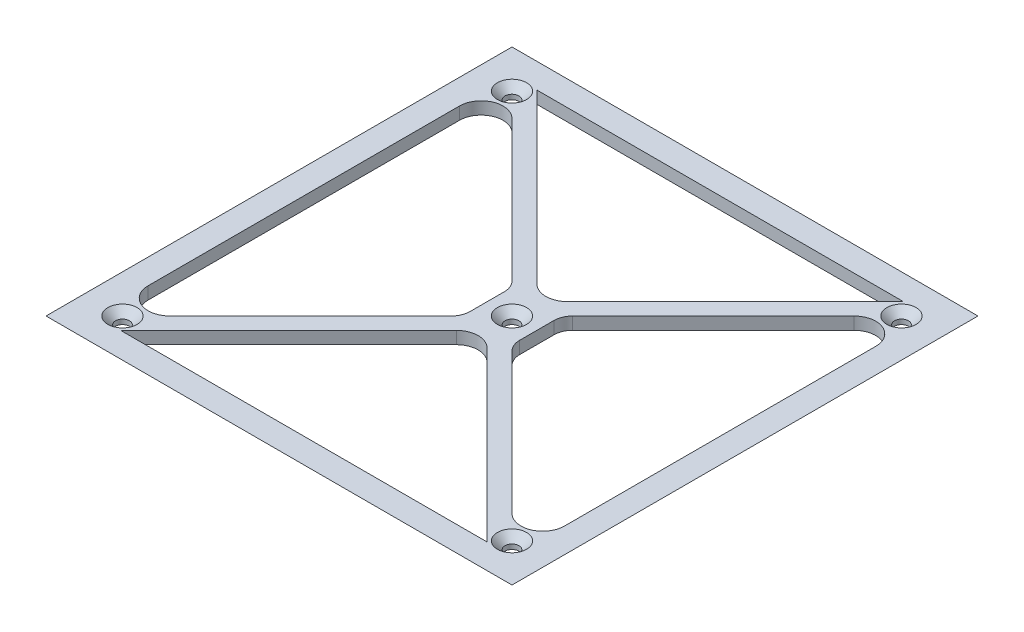
SolidWorks part; units mm, degrees
ref_plane "Front Plane" through (0, 0, 0) normal (0, 0, 1) x (1, 0, 0)
ref_plane "Top Plane" through (0, 0, 0) normal (0, 1, 0) x (1, 0, 0)
ref_plane "Right Plane" through (0, 0, 0) normal (1, 0, 0) x (0, 0, -1)
sketch "Sketch1" plane through (0, 0, 0) normal (0, 1, 0) x (1, 0, 0)
  line L0 (-67, -75) -> (-33.5682, -41.5682)
  line L1 (-75, -75) -> (75, -75)
  line L2 (-75, -75) -> (-75, 75)
  line L3 (-75, 75) -> (75, 75)
  line L4 (75, -75) -> (75, 75)
  line L5 (-75, -75) -> (75, 75) construction
  line L6 (-75, 75) -> (75, -75) construction
  line L7 (-67, -67) -> (-16, -67)
  line L8 (-67, -50.1005) -> (-67, 50.1005)
  line L9 (-67, 67) -> (-16, 67)
  line L10 (67, -50.1005) -> (67, 50.1005)
  line L11 (-67, -67) -> (67, 67) construction
  line L12 (-67, 67) -> (67, -67) construction
  line L13 (0, 75) -> (0, -75)
  line L14 (67, -75) -> (33.5682, -41.5682)
  line L15 (-75, 0) -> (75, 0)
  line L16 (-67, 75) -> (-33.5682, 41.5682)
  line L17 (67, 75) -> (33.5682, 41.5682)
  line L18 (-8, -5.5147) -> (-8, 5.5147)
  line L19 (8, -5.5147) -> (8, 5.5147)
  line L20 (-22.3189, 30.3189) -> (-4.9497, 12.9497)
  line L21 (22.3189, 30.3189) -> (4.9497, 12.9497)
  line L22 (-22.3189, -30.3189) -> (-4.9497, -12.9497)
  line L23 (22.3189, -30.3189) -> (4.9497, -12.9497)
  line L24 (-33.5682, 41.5682) -> (-22.3189, 30.3189)
  line L27 (-16, 67) -> (16, 67)
  line L28 (16, -67) -> (67, -67)
  line L29 (33.5682, 41.5682) -> (22.3189, 30.3189)
  line L30 (16, 67) -> (67, 67)
  line L31 (-55.0503, -55.0503) -> (-9.7574, -9.7574)
  line L32 (9.7574, -9.7574) -> (55.0503, -55.0503)
  line L33 (-55.0503, 55.0503) -> (-9.7574, 9.7574)
  line L34 (9.7574, 9.7574) -> (55.0503, 55.0503)
  line L35 (-16, -67) -> (16, -67)
  line L36 (-33.5682, -41.5682) -> (-22.3189, -30.3189)
  line L37 (22.3189, -30.3189) -> (33.5682, -41.5682)
  arc A14 (4.9497, -12.9497) -> (-4.9497, -12.9497) centre (0, -17.8995) ccw
  arc A15 (4.9497, 12.9497) -> (-4.9497, 12.9497) centre (0, 17.8995) cw
  arc A16 (67, -50.1005) -> (55.0503, -55.0503) centre (60, -50.1005) cw
  arc A17 (-55.0503, -55.0503) -> (-67, -50.1005) centre (-60, -50.1005) cw
  arc A18 (67, 50.1005) -> (55.0503, 55.0503) centre (60, 50.1005) ccw
  arc A19 (-67, 50.1005) -> (-55.0503, 55.0503) centre (-60, 50.1005) cw
  arc A24 (-8, -5.5147) -> (-9.7574, -9.7574) centre (-14, -5.5147) cw
  arc A25 (8, -5.5147) -> (9.7574, -9.7574) centre (14, -5.5147) ccw
  arc A26 (9.7574, 9.7574) -> (8, 5.5147) centre (14, 5.5147) ccw
  arc A27 (-8, 5.5147) -> (-9.7574, 9.7574) centre (-14, 5.5147) ccw
  point P0 (0, 0)
  point P6 (0, 0)
  point P52 (24, -32)
  point P55 (-24, -32)
  point P58 (24, 32)
  point P61 (-24, 32)
  point P64 (0, -8)
  point P67 (0, 8)
  point P94 (-8, -8)
  point P97 (8, -8)
  point P100 (8, 8)
  point P103 (-8, 8)
  dimension "D11" = 7
  dimension "D12" = 7
  dimension "D14" = 6
  dimension "D1" = 150
  dimension "D2" = 134
  dimension "D3" = 45
  dimension "D4" = 94.7523
  dimension "D6" = 8
extrude "Boss-Extrude2" add sketch "Sketch1" along normal blind 4 contours L18 A24 L31 A17 L8 L15 L2 L1 L0 L7 L13 L22 A14 | A27 L18 L15 L13 A15 L20 L3 L9 L16 L2 L8 A19 L33 | A26 L34 A18 L10 L15 L4 L3 L17 L30 L13 L21 A15 L19 | A25 L19 L15 L13 A14 L23 L1 L28 L14 L4 L10 A16 L32 | L35 L7 L0 L1 L13 | L35 L13 L1 L14 L28 | L9 L27 L13 L3 L16 | L27 L30 L17 L3 L13 region at (-71, 0, 73.9393) region at (-31.5423, 0, 71.0847) region at (31.5423, 0, 71.0847) region at (-73.9393, 0, -37.5) region at (63.75, 0, 70.25) region at (-31.5423, 0, -71.0847) region at (71, 0, -1.0607) region at (31.5423, 0, -71.0847)
sketch "Sketch2" plane through (0, 4, 0) normal (0, 1, 0) x (1, 0, 0)
  line L0 (-67, 50.1005) -> (-67, 75)
  line L1 (-75, 75) -> (75, 75) construction
  line L2 (-59, 67) -> (-75, 67)
  line L3 (-75, -75) -> (-75, 75) construction
  line L4 (0, -75) -> (0, 75)
  line L5 (-75, -75) -> (75, -75) construction
  line L6 (-75, 0) -> (75, 0)
  line L7 (75, -75) -> (75, 75) construction
  circle A0 centre (-62.6878, 62.6878) radius 4.3122
  circle A1 centre (-62.6878, 62.6878) radius 3
  circle A2 centre (62.6878, 62.6878) radius 3
  circle A3 centre (62.6878, -62.6878) radius 3
  circle A4 centre (-62.6878, -62.6878) radius 3
  circle A5 centre (0, 0) radius 3
  point P11 (-62.6878, 62.6878)
  point P21 (62.6878, 62.6878)
  point P23 (62.6878, -62.6878)
  point P25 (-62.6878, -62.6878)
  point P27 (0, 0)
  dimension "D1" = 8.6243
  dimension "D2" = 6
  dimension "D3" = 6
hole_wizard "CSK for M4 Flat Head Machine Screw1" positions "Sketch2" profile "Sketch5" countersink size "M4" standard "ANSI Metric" end condition through all
sketch "Sketch5" plane through (0, 4, 0) normal (1, 0, 0) x (0, 0, 1)
  line L0 (0, 0) -> (0, 4)
  line L1 (0, 4) -> (2.25, 4)
  line L2 (2.25, 4) -> (2.25, 2.45)
  line L3 (2.25, 2.45) -> (4.7, 0)
  line L5 (4.7, 0) -> (0, 0)
  line L6 (-2.25, 2.45) -> (-4.7, 0) construction
  line L11 (0, -6.35) -> (0, 107.95) construction
  dimension "Thru Hole Dia." = 4.5
  dimension "Thru Hole Depth" = 4
  dimension "Near C'Sink Dia." = 9.4
  dimension "Near C'Sink Angle" = 90
chamfer "Chamfer2" distance 4 angle 45 4 edges at (0, 0, 75) (-75, 0, 0) (0, 0, -75) (75, 0, 0)
